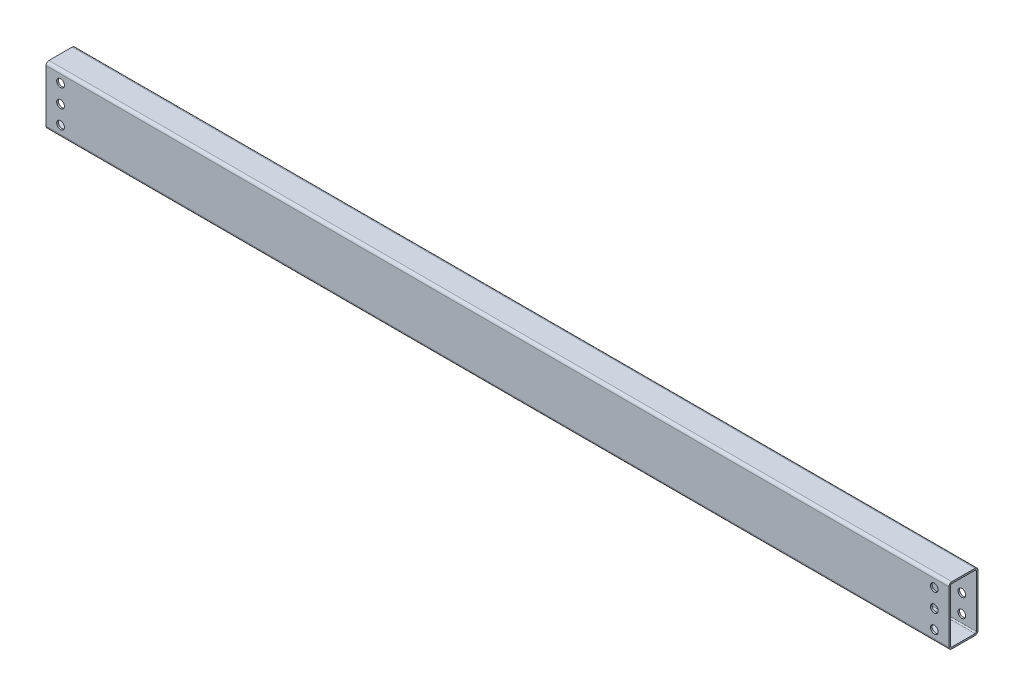
SolidWorks part; units mm, degrees
material "6061-T6 (SS)"
ref_plane "Front" through (0, 0, 0) normal (0, 0, 1) x (1, 0, 0)
ref_plane "Top" through (0, 0, 0) normal (0, 1, 0) x (1, 0, 0)
ref_plane "Right" through (0, 0, 0) normal (1, 0, 0) x (0, 0, -1)
sketch "Sketch1" plane through (0, 0, 0) normal (1, 0, 0) x (0, 0, -1)
  line L0 (10.16, -25.4) -> (-10.16, -25.4)
  line L1 (12.7, -22.86) -> (12.7, 22.86)
  line L2 (10.16, 25.4) -> (-10.16, 25.4)
  line L3 (-12.7, -22.86) -> (-12.7, 22.86)
  line L4 (12.7, -25.4) -> (-12.7, 25.4) construction
  line L5 (12.7, 25.4) -> (-12.7, -25.4) construction
  arc A0 (-10.16, -25.4) -> (-12.7, -22.86) centre (-10.16, -22.86) cw
  arc A1 (10.16, -25.4) -> (12.7, -22.86) centre (10.16, -22.86) ccw
  arc A2 (12.7, 22.86) -> (10.16, 25.4) centre (10.16, 22.86) ccw
  arc A3 (-10.16, 25.4) -> (-12.7, 22.86) centre (-10.16, 22.86) ccw
  point P0 (0, 0)
  dimension "D3" = 2.54
  dimension "D1" = 25.4
  dimension "D2" = 50.8
extrude "Extrude-Thin1" add sketch "Sketch1" along normal mid plane 787.4 thin thin type one direction reverse wall 1.4478
hole_wizard "1/4 Clearance Hole1" positions "Sketch2" profile "Sketch3" hole size "1/4" standard "ANSI Inch" end condition through all
sketch "Sketch2" plane through (0, 0, -12.7) normal (0, 0, -1) x (-1, 0, 0)
  line L0 (-393.7, -22.86) -> (-393.7, 22.86) construction
  line L1 (-393.7, 25.4) -> (393.7, 25.4) construction
  line L2 (-393.7, -25.4) -> (393.7, -25.4) construction
  line L3 (-381, 15.875) -> (-381, -15.875) construction
  line L4 (0, 0) -> (0, -37.3791) construction
  point P0 (-381, 15.875)
  point P2 (-381, -15.875)
  point P15 (-381, 0)
  point P23 (381, -15.875)
  point P24 (381, 0)
  point P25 (381, 15.875)
  dimension "D1" = 12.7
  dimension "D2" = 9.525
  dimension "D3" = 9.525
sketch "Sketch3" plane through (381, 15.875, -12.7) normal (1, 0, 0) x (0, 1, 0)
  line L0 (0, 0) -> (0, 25.4)
  line L1 (0, 25.4) -> (3.3782, 25.4)
  line L2 (3.3782, 25.4) -> (3.3782, 0)
  line L5 (3.3782, 0) -> (0, 0)
  line L11 (0, -6.35) -> (0, 107.95) construction
  dimension "Thru Hole Dia." = 6.7564
  dimension "Thru Hole Depth" = 25.4
hole_wizard "1/4 Clearance Hole2" positions "Sketch4" profile "Sketch5" hole size "1/4" standard "ANSI Inch" end condition up to next
sketch "Sketch4" plane through (0, 0, -12.7) normal (0, 0, -1) x (-1, 0, 0)
  line L0 (-234.95, 15.875) -> (-234.95, -15.875) construction
  line L2 (-393.7, 25.4) -> (393.7, 25.4) construction
  line L3 (-393.7, -25.4) -> (393.7, -25.4) construction
  line L4 (0, 0) -> (0, -51.4899) construction
  point P19 (-234.95, 15.875)
  point P21 (-234.95, 0)
  point P23 (-234.95, -15.875)
  point P42 (234.95, -15.875)
  point P43 (234.95, 0)
  point P44 (234.95, 15.875)
  dimension "D1" = 9.525
  dimension "D2" = 9.525
  dimension "D3" = 469.9
sketch "Sketch5" plane through (234.95, 15.875, -12.7) normal (1, 0, 0) x (0, 1, 0)
  line L0 (0, 0) -> (0, 1.4478)
  line L1 (0, 1.4478) -> (3.3782, 1.4478)
  line L2 (3.3782, 1.4478) -> (3.3782, 0)
  line L5 (3.3782, 0) -> (0, 0)
  line L11 (0, -6.35) -> (0, 107.95) construction
  dimension "Thru Hole Dia." = 6.7564
  dimension "Thru Hole Depth" = 1.4478
sketch "Sketch6" plane through (0, 0, -12.7) normal (0, 0, -1) x (-1, 0, 0)
  line L0 (-393.7, -25.4) -> (393.7, -25.4) construction
  line L2 (-120.65, -25.4) -> (-107.95, -25.4)
  line L3 (-120.65, -25.4) -> (-120.65, 15.875)
  line L4 (-117.475, 19.05) -> (-111.125, 19.05)
  line L5 (-107.95, -25.4) -> (-107.95, 15.875)
  line L6 (-44.45, -25.4) -> (-31.75, -25.4)
  line L11 (-44.45, -25.4) -> (-44.45, 15.875)
  line L12 (-41.275, 19.05) -> (-34.925, 19.05)
  line L13 (-31.75, -25.4) -> (-31.75, 15.875)
  line L14 (31.75, -25.4) -> (44.45, -25.4)
  line L15 (31.75, -25.4) -> (31.75, 15.875)
  line L16 (34.925, 19.05) -> (41.275, 19.05)
  line L17 (44.45, -25.4) -> (44.45, 15.875)
  line L18 (107.95, -25.4) -> (120.65, -25.4)
  line L19 (107.95, -25.4) -> (107.95, 15.875)
  line L20 (111.125, 19.05) -> (117.475, 19.05)
  line L21 (120.65, -25.4) -> (120.65, 15.875)
  line L22 (0, 0) -> (0, -9.525) construction
  arc A0 (-111.125, 19.05) -> (-107.95, 15.875) centre (-111.125, 15.875) cw
  arc A1 (-120.65, 15.875) -> (-117.475, 19.05) centre (-117.475, 15.875) cw
  arc A4 (-34.925, 19.05) -> (-31.75, 15.875) centre (-34.925, 15.875) cw
  arc A5 (-44.45, 15.875) -> (-41.275, 19.05) centre (-41.275, 15.875) cw
  arc A6 (41.275, 19.05) -> (44.45, 15.875) centre (41.275, 15.875) cw
  arc A7 (31.75, 15.875) -> (34.925, 19.05) centre (34.925, 15.875) cw
  arc A8 (117.475, 19.05) -> (120.65, 15.875) centre (117.475, 15.875) cw
  arc A9 (107.95, 15.875) -> (111.125, 19.05) centre (111.125, 15.875) cw
  dimension "D1" = 3.175
  dimension "D2" = 12.7
  dimension "D3" = 44.45
  dimension "D5" = 76.2
  dimension "D4" = 4
extrude "Cut-Extrude1" cut sketch "Sketch6" against normal blind 9.525
